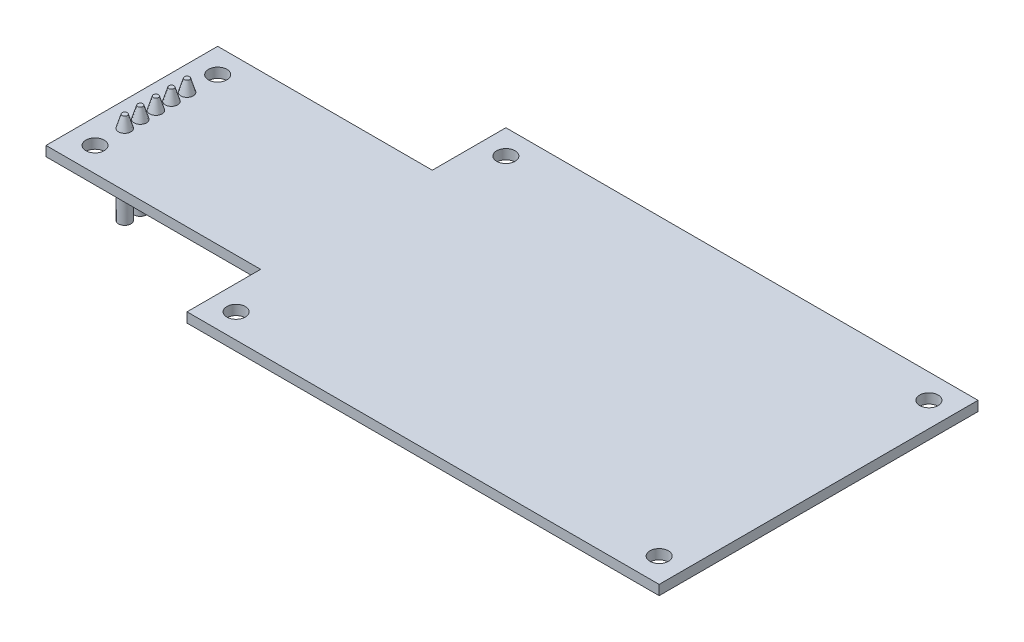
SolidWorks part; units mm, degrees
ref_plane "Plan de face" through (0, 0, 0) normal (0, 0, 1) x (1, 0, 0)
ref_plane "Plan de dessus" through (0, 0, 0) normal (0, 1, 0) x (1, 0, 0)
ref_plane "Plan de droite" through (0, 0, 0) normal (1, 0, 0) x (0, 0, -1)
sketch "Esquisse1" plane through (0, 0, 0) normal (0, 1, 0) x (1, 0, 0)
  line L1 (0, 0) -> (77, 0)
  line L2 (0, 0) -> (0, 52)
  line L3 (0, 52) -> (77, 52)
  line L4 (77, 0) -> (77, 52)
  line L5 (0, 12) -> (-35, 12)
  line L6 (0, 12) -> (0, 40)
  line L7 (0, 40) -> (-35, 40)
  line L8 (-35, 12) -> (-35, 40)
  dimension "D1" = 77
  dimension "D2" = 52
  dimension "D3" = 35
  dimension "D4" = 12
  dimension "D5" = 12
  dimension "D6" = 28
extrude "Boss.-Extru.1" add sketch "Esquisse1" along normal blind 1.6 contours L8 L5 L2 L7 | L1 L4 L3 L2 region at (38.5, 0, -26) region at (-17.5, 0, -26)
sketch "Esquisse2" plane through (0, 1.6, 0) normal (0, 1, 0) x (1, 0, 0)
  line L0 (0, 40) -> (-35, 40) construction
  line L1 (-35, 12) -> (-35, 40) construction
  line L2 (0, 12) -> (-35, 12) construction
  line L3 (0, 0) -> (77, 0) construction
  line L4 (0, 0) -> (0, 12) construction
  line L5 (77, 0) -> (77, 52) construction
  line L6 (0, 52) -> (77, 52) construction
  line L7 (0, 40) -> (0, 52) construction
  circle A0 centre (-31, 36) radius 1.5
  circle A1 centre (-31, 16) radius 1.5
  circle A2 centre (4, 4) radius 1.5
  circle A3 centre (4, 48) radius 1.5
  circle A4 centre (73, 48) radius 1.5
  circle A5 centre (73, 4) radius 1.5
  dimension "D1" = 4
  dimension "D3" = 3
  dimension "D5" = 4
  dimension "D6" = 3
  dimension "D8" = 4
  dimension "D9" = 3
  dimension "D10" = 4
  dimension "D11" = 4
  dimension "D12" = 3
  dimension "D13" = 3
  dimension "D14" = 4
  dimension "D15" = 4
  dimension "D16" = 3
  dimension "D17" = 4
  dimension "D18" = 4
  dimension "D2" = 4
  dimension "D4" = 4
  dimension "D7" = 4
extrude "Enlèv. mat.-Extru.1" cut sketch "Esquisse2" against normal up to next
sketch "Esquisse3" plane through (0, 1.6, 0) normal (0, 1, 0) x (1, 0, 0)
  line L0 (-35, 12) -> (-35, 40) construction
  line L1 (0, 40) -> (-35, 40) construction
  circle A0 centre (-31, 31) radius 1.016
  circle A1 centre (-31, 28.46) radius 1.016
  circle A2 centre (-31, 25.92) radius 1.016
  circle A3 centre (-31, 23.38) radius 1.016
  circle A4 centre (-31, 20.84) radius 1.016
  dimension "D1" = 2.032
  dimension "D2" = 4
  dimension "D3" = 9
  dimension "D4" = 5
extrude "Boss.-Extru.2" add sketch "Esquisse3" along normal blind 2 and the other way blind 13
chamfer "Chanfrein1" distance 2 distance2 0.6 5 edges at (-31, 3.6, -19.824) (-31, 3.6, -22.364) (-31, 3.6, -24.904) (-31, 3.6, -27.444) (-31, 3.6, -29.984) first distance on face at (-31, 1.6, -19.824) first distance on face at (-31, 1.6, -22.364) first distance on face at (-31, 1.6, -24.904) first distance on face at (-31, 1.6, -27.444) first distance on face at (-31, 1.6, -29.984)
